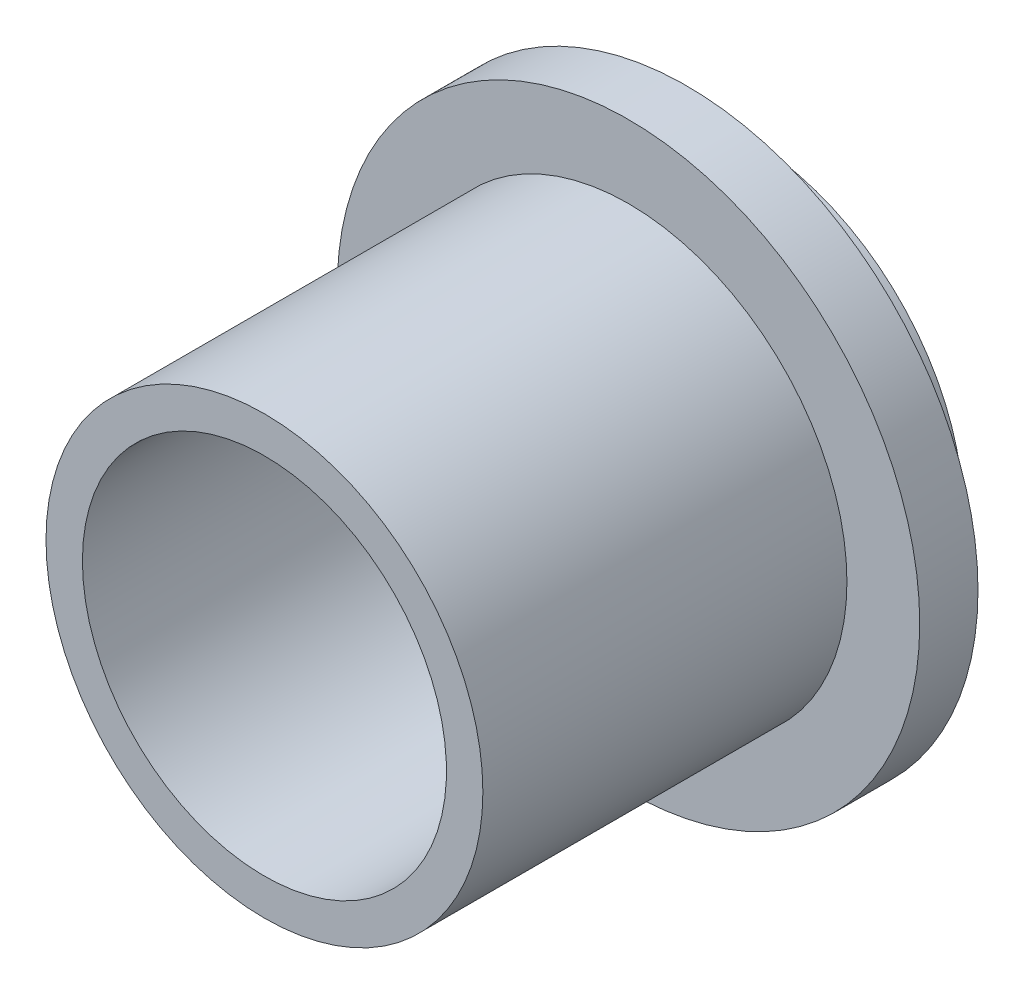
SolidWorks part; units mm, degrees
material "1060 Alloy"
ref_plane "Front Plane" through (0, 0, 0) normal (0, 0, 1) x (1, 0, 0)
ref_plane "Top Plane" through (0, 0, 0) normal (0, 1, 0) x (1, 0, 0)
ref_plane "Right Plane" through (0, 0, 0) normal (1, 0, 0) x (0, 0, -1)
sketch "Sketch1" plane through (0, 0, 0) normal (0, 0, 1) x (1, 0, 0)
  circle A0 centre (0, 0) radius 31.75
  circle A1 centre (0, 0) radius 38.1
  dimension "D1" = 63.5
  dimension "D2" = 76.2
extrude "Boss-Extrude1" add sketch "Sketch1" along normal blind 63.5
ref_plane "Plane1" through (0, 0, 0) normal (0, 0, -1) x (-1, 0, 0)
sketch "Sketch2" plane through (0, 0, 0) normal (0, 0, -1) x (-1, 0, 0)
  circle A0 centre (0, 0) radius 50.8
  dimension "D1" = 101.6
extrude "Boss-Extrude2" add sketch "Sketch2" along normal blind 10.16
sketch "Sketch3" plane through (0, 0, 0) normal (0, 0, -1) x (-1, 0, 0)
  circle A0 centre (0, 0) radius 31.75
  dimension "D1" = 63.5
extrude "Cut-Extrude2" cut sketch "Sketch3" against normal through all and the other way blind 53.34 contours A0
ref_plane "Plane2" through (0, 0, -10.16) normal (0, 0, -1) x (-1, 0, 0)
sketch "Sketch4" plane through (0, 0, -10.16) normal (0, 0, -1) x (-1, 0, 0)
  circle A0 centre (0, 0) radius 31.75
  circle A1 centre (0, 0) radius 38.1
  dimension "D1" = 63.5
  dimension "D2" = 76.2
extrude "Boss-Extrude3" add sketch "Sketch4" along normal blind 10.16
